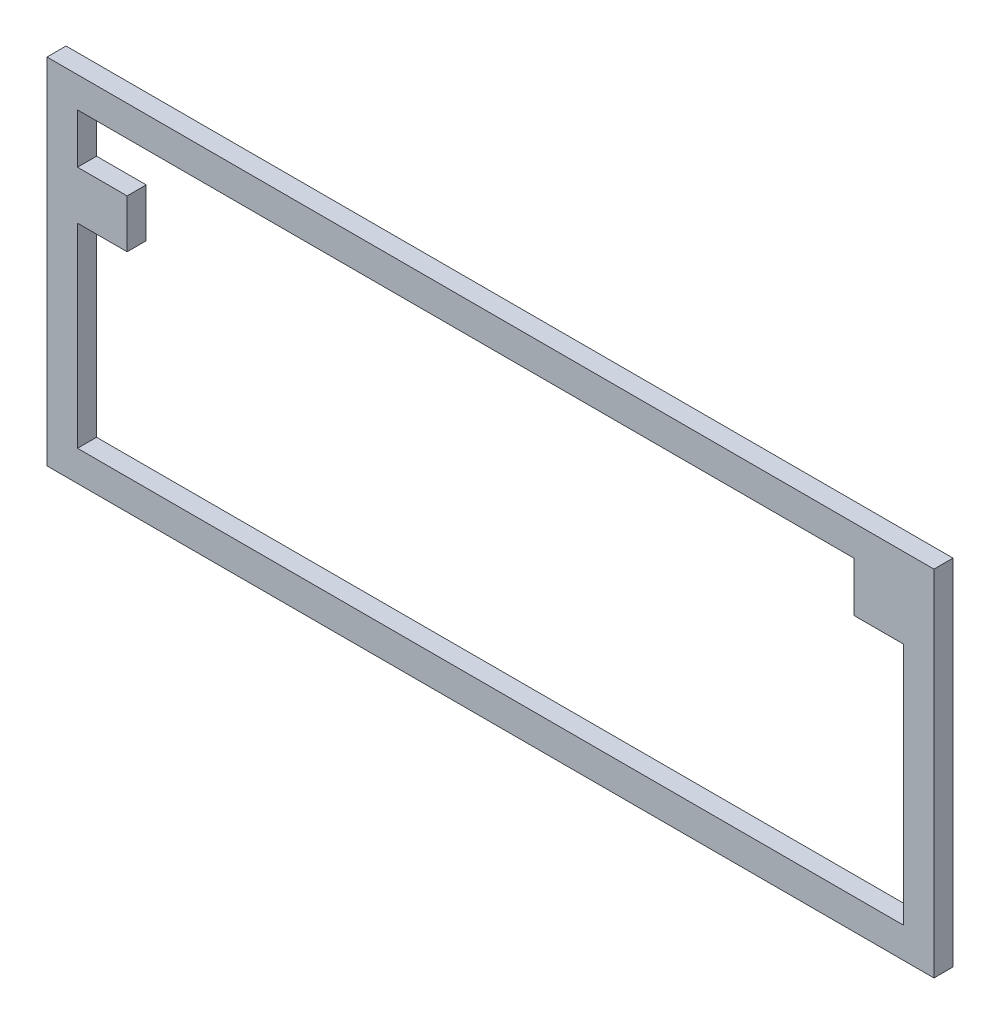
SolidWorks part; units mm, degrees
ref_plane "Front Plane" through (0, 0, 0) normal (0, 0, 1) x (1, 0, 0)
ref_plane "Top Plane" through (0, 0, 0) normal (0, 1, 0) x (1, 0, 0)
ref_plane "Right Plane" through (0, 0, 0) normal (1, 0, 0) x (0, 0, -1)
sketch "Sketch1" plane through (0, 0, 0) normal (0, 0, 1) x (1, 0, 0)
  line L0 (-159.2246, 38.0997) -> (-131.7721, 38.0997) construction
  line L1 (-159.2246, 57.6246) -> (165.5748, 57.6246) construction
  line L2 (-159.2246, 57.6246) -> (-159.2246, -57.6248) construction
  line L3 (-159.2246, -57.6248) -> (165.5748, -57.6248)
  line L4 (165.5748, 57.6246) -> (165.5748, -57.6248) construction
  line L5 (-171.2246, 69.6246) -> (177.5748, 69.6246)
  line L6 (-171.2246, 69.6246) -> (-171.2246, -69.6248)
  line L7 (-171.2246, -69.6248) -> (177.5748, -69.6248)
  line L8 (177.5748, 69.6246) -> (177.5748, -69.6248)
  line L9 (-159.2246, 19.0504) -> (-122.1563, 19.0504) construction
  line L10 (-159.2246, 57.6246) -> (-159.2246, 38.0997)
  line L11 (-159.2246, 38.0997) -> (-139.6995, 38.0997)
  line L12 (-139.6995, 38.0997) -> (-139.6995, 19.0504)
  line L13 (-139.6995, 57.6246) -> (-139.6995, 17.7572) construction
  line L14 (-139.6995, 19.0504) -> (-159.2246, 19.0504)
  line L15 (-159.2246, 19.0504) -> (-159.2246, -57.6248)
  line L20 (-159.2246, 57.6246) -> (146.0498, 57.6246)
  line L21 (146.0498, 57.6246) -> (146.0498, 38.0997)
  line L22 (146.0498, 38.0997) -> (165.5748, 38.0997)
  line L23 (165.5748, 38.0997) -> (146.0498, 38.0997) construction
  line L24 (165.5748, 38.0997) -> (165.5748, -57.6248)
  line L29 (146.0498, 38.0997) -> (146.0498, 57.6246) construction
  dimension "D1" = 159.2246
  dimension "D2" = 115.2494
  dimension "D3" = 57.6246
  dimension "D4" = 324.7994
  dimension "D5" = 12
  dimension "D6" = 12
  dimension "D7" = 12
  dimension "D8" = 12
  dimension "D9" = 38.5742
  dimension "D11" = 19.5249
  dimension "D12" = 19.5251
  dimension "D14" = 19.5249
  dimension "D15" = 19.525
extrude "Boss-Extrude1" add sketch "Sketch1" against normal blind 7.5
